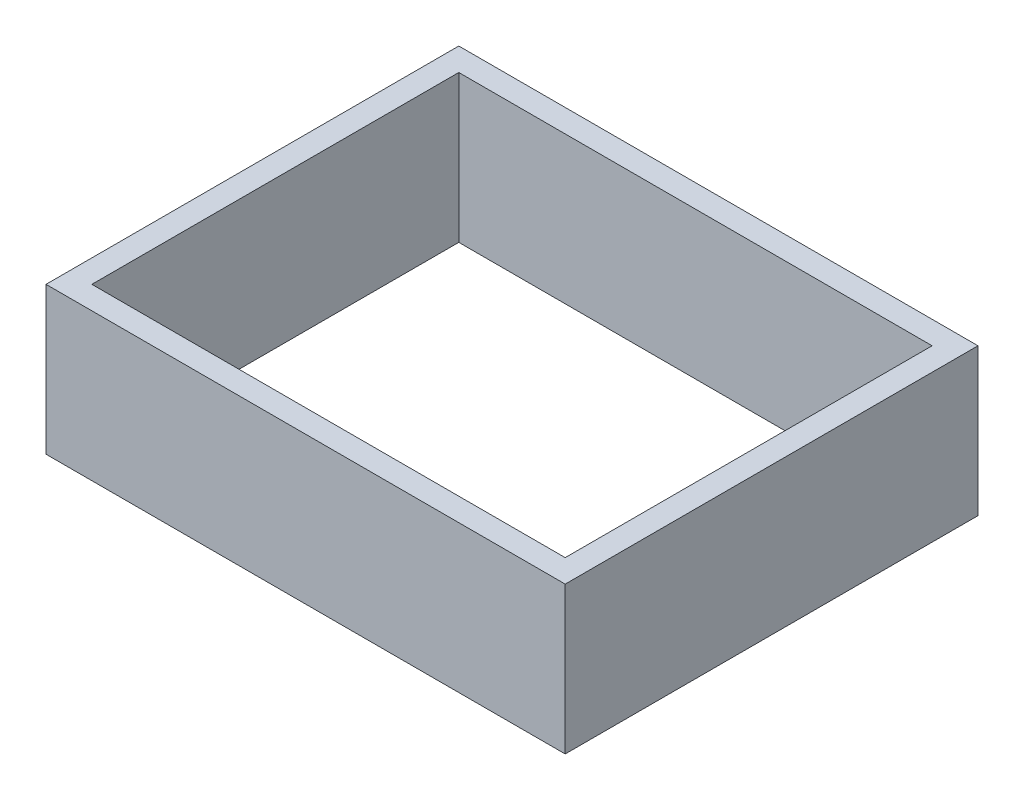
SolidWorks part; units mm, degrees
ref_plane "Front Plane" through (0, 0, 0) normal (0, 0, 1) x (1, 0, 0)
ref_plane "Top Plane" through (0, 0, 0) normal (0, 1, 0) x (1, 0, 0)
ref_plane "Right Plane" through (0, 0, 0) normal (1, 0, 0) x (0, 0, -1)
sketch "Sketch1" plane through (0, 0, 0) normal (0, 1, 0) x (1, 0, 0)
  line L1 (0, 0) -> (283, 0)
  line L2 (0, 0) -> (0, 225)
  line L3 (0, 225) -> (283, 225)
  line L4 (283, 0) -> (283, 225)
  dimension "D1" = 225
  dimension "D2" = 283
extrude "Boss-Extrude1" add sketch "Sketch1" along normal blind 80.2 contours L1 L4 L3 L2
sketch "Sketch2" plane through (0, 80.2, 0) normal (0, 1, 0) x (1, 0, 0)
  line L14 (12.5, 12.5) -> (270.5, 12.5)
  line L15 (270.5, 12.5) -> (270.5, 212.5)
  line L16 (270.5, 212.5) -> (12.5, 212.5)
  line L17 (12.5, 212.5) -> (12.5, 12.5)
  line L18 (12.5, 12.5) -> (270.5, 12.5)
  line L19 (270.5, 12.5) -> (270.5, 212.5)
  line L20 (270.5, 212.5) -> (12.5, 212.5)
  line L21 (12.5, 212.5) -> (12.5, 12.5)
  dimension "D1" = 12.5
extrude "Cut-Extrude1" cut sketch "Sketch2" against normal up to surface (80.2 mm away) contours L21 L18 L19 L20 up to face at (141.5, 0, -112.5)
